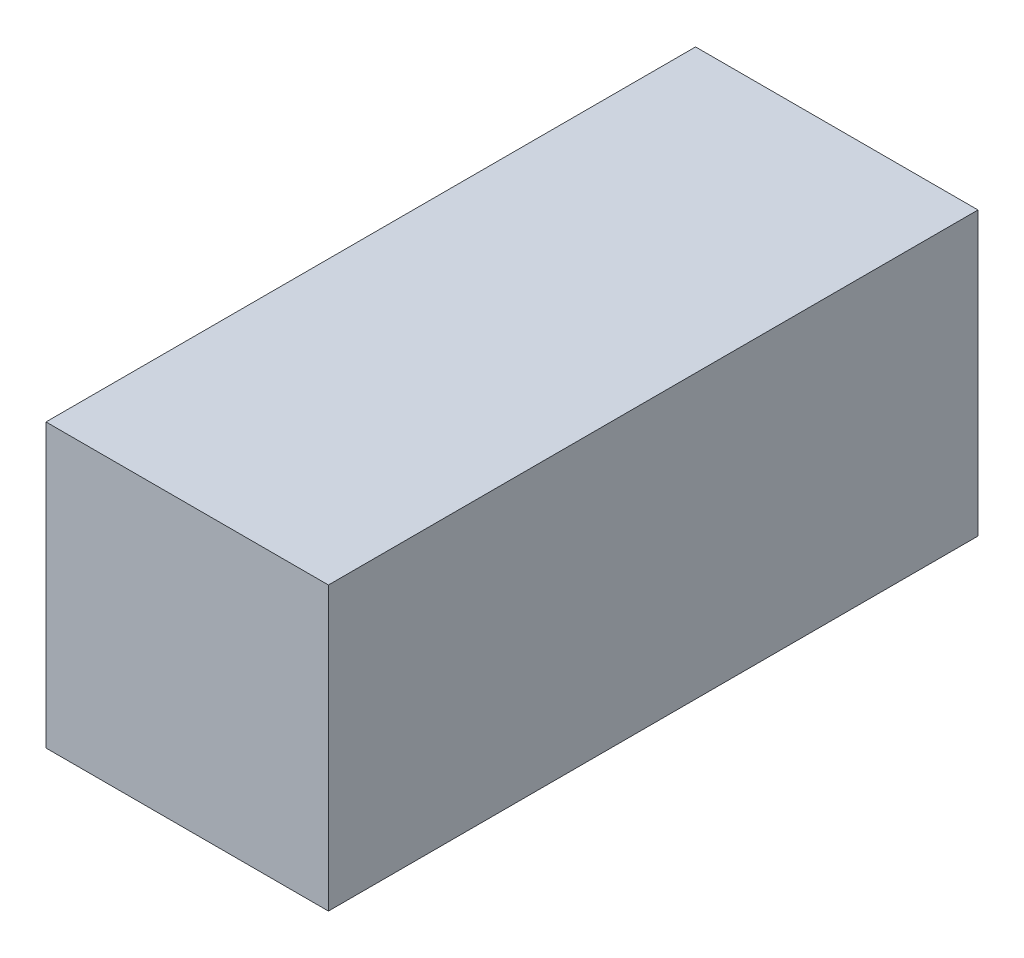
SolidWorks part; units mm, degrees
ref_plane "Front Plane" through (0, 0, 0) normal (0, 0, 1) x (1, 0, 0)
ref_plane "Top Plane" through (0, 0, 0) normal (0, 1, 0) x (1, 0, 0)
ref_plane "Right Plane" through (0, 0, 0) normal (1, 0, 0) x (0, 0, -1)
sketch "Sketch1" plane through (0, 0, 0) normal (0, 0, 1) x (1, 0, 0)
  line L1 (-50, -50) -> (50, -50)
  line L2 (-50, -50) -> (-50, 50)
  line L3 (-50, 50) -> (50, 50)
  line L4 (50, -50) -> (50, 50)
  line L5 (-50, -50) -> (50, 50) construction
  line L6 (-50, 50) -> (50, -50) construction
  point P0 (0, 0)
  dimension "D1" = 100
extrude "Boss-Extrude1" add sketch "Sketch1" along normal blind 230
ref_plane "Plane1" through (0, 0, 0) normal (-0.7071, 0.7071, 0) x (0.7071, 0.7071, 0)
ref_plane "Plane2" through (0, 0, 0) normal (-0.7071, -0.7071, 0) x (-0.7071, 0.7071, 0)
ref_axis "Axis1" through (0, 0, -11.5) along (0, 0, 1)
